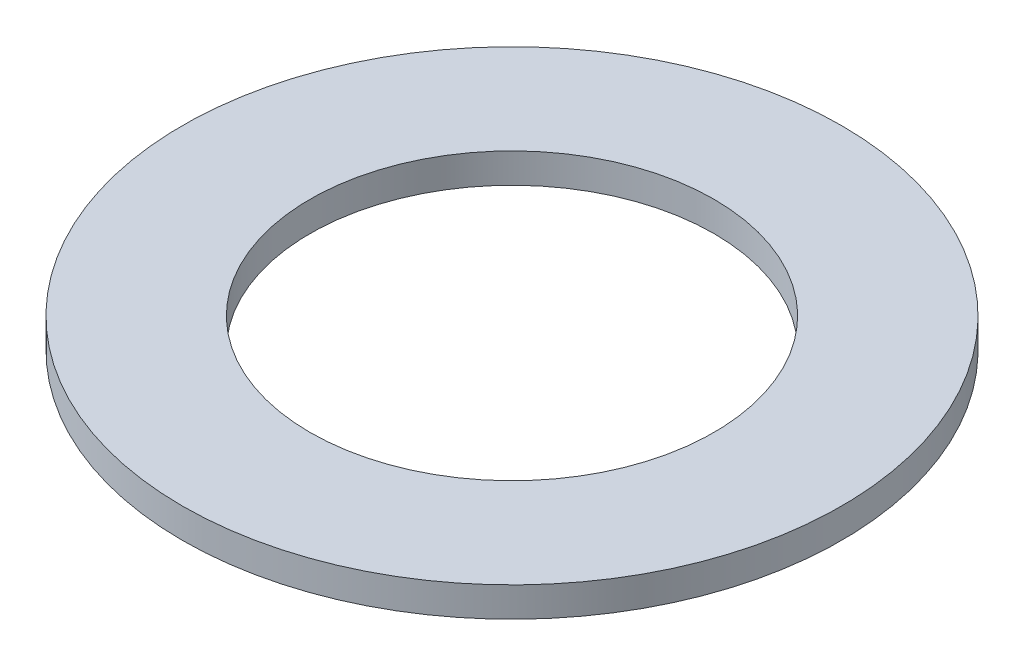
SolidWorks part; units mm, degrees
ref_plane "Front Plane" through (0, 0, 0) normal (0, 0, 1) x (1, 0, 0)
ref_plane "Top Plane" through (0, 0, 0) normal (0, 1, 0) x (1, 0, 0)
ref_plane "Right Plane" through (0, 0, 0) normal (1, 0, 0) x (0, 0, -1)
sketch "Sketch1" plane through (0, 0, 0) normal (0, 1, 0) x (1, 0, 0)
  circle A0 centre (0, 0) radius 77.5
  dimension "FLANGE_OD" = 155
extrude "Boss-Extrude1" add sketch "Sketch1" along normal blind 7
sketch "Sketch2" plane through (0, 0, 0) normal (0, 1, 0) x (1, 0, 0)
  circle A0 centre (0, 0) radius 47.5
  dimension "BORE_D" = 95
extrude "Cut-Extrude1" cut sketch "Sketch2" along normal through all
sketch "Sketch3" plane through (0, 7, 0) normal (0, 1, 0) x (1, 0, 0)
  circle A0 centre (0, 0) radius 28.9395 construction
  circle A1 centre (-28.9395, 0) radius 4.5072
  dimension "BOLT_D" = 9.0143
  dimension "BOLT_PCD" = 57.879
extrude "Cut-Extrude2" cut sketch "Sketch3" against normal blind 5.4623 rebuild error yes
pattern_circular "CirPattern1" count 6 over 360 rebuild error yes
